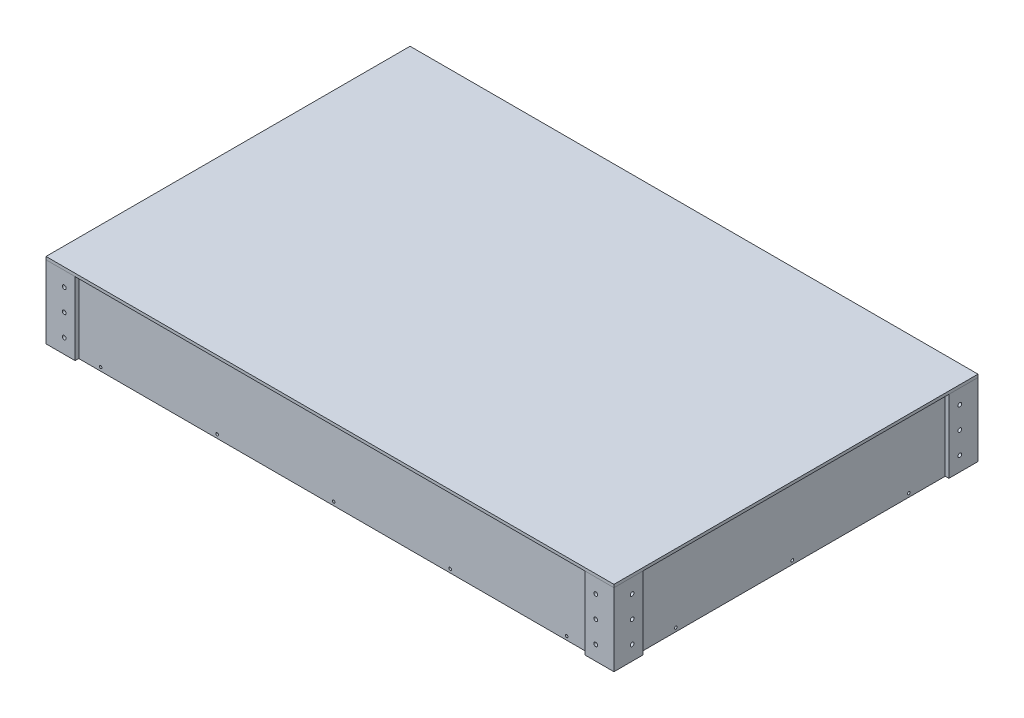
SolidWorks part; units mm, degrees
ref_plane "Front" through (0, 0, 0) normal (0, 0, 1) x (1, 0, 0)
ref_plane "Top" through (0, 0, 0) normal (0, 1, 0) x (1, 0, 0)
ref_plane "Right" through (0, 0, 0) normal (1, 0, 0) x (0, 0, -1)
sketch "Sketch1" plane through (0, 0, 0) normal (0, 1, 0) x (1, 0, 0)
  line L1 (-241.3, 152.4) -> (241.3, 152.4)
  line L2 (-241.3, 152.4) -> (-241.3, -152.4)
  line L3 (-241.3, -152.4) -> (241.3, -152.4)
  line L4 (241.3, 152.4) -> (241.3, -152.4)
  line L5 (-241.3, 152.4) -> (241.3, -152.4) construction
  line L6 (-241.3, -152.4) -> (241.3, 152.4) construction
  point P0 (0, 0)
  dimension "D1" = 482.6
  dimension "D2" = 304.8
extrude "Boss-Extrude1" add sketch "Sketch1" along normal blind 6.35
sketch "Sketch2" plane through (0, 6.35, 0) normal (0, 1, 0) x (1, 0, 0)
  line L0 (241.3, -152.4) -> (241.3, 152.4) construction
  line L1 (-241.3, 152.4) -> (241.3, 152.4)
  line L2 (-241.3, 152.4) -> (-241.3, 155.575)
  line L3 (-241.3, 155.575) -> (241.3, 155.575)
  line L4 (241.3, 152.4) -> (241.3, 155.575)
  line L5 (-241.3, 152.4) -> (241.3, 155.575) construction
  line L6 (-241.3, 155.575) -> (241.3, 152.4) construction
  line L7 (-241.3, -155.575) -> (241.3, -155.575)
  line L8 (-241.3, -155.575) -> (-241.3, -152.4)
  line L9 (-241.3, -152.4) -> (241.3, -152.4)
  line L10 (241.3, -155.575) -> (241.3, -152.4)
  line L11 (-241.3, -155.575) -> (241.3, -152.4) construction
  line L12 (-241.3, -152.4) -> (241.3, -155.575) construction
  line L13 (-241.3, 152.4) -> (-241.3, -152.4) construction
  line L14 (241.3, 152.4) -> (-241.3, 152.4) construction
  line L15 (-241.3, -152.4) -> (241.3, -152.4) construction
  point P0 (0, 153.9875)
  point P5 (0, -153.9875)
  dimension "D1" = 3.175
extrude "Boss-Extrude2" add sketch "Sketch2" along normal blind 57.15 and the other way up to surface (6.35 mm away) separate body other way up to face at (0, 0, 0)
sketch "Sketch3" plane through (0, 6.35, 0) normal (0, 1, 0) x (1, 0, 0)
  line L0 (241.3, -155.575) -> (-241.3, -155.575) construction
  line L1 (-241.3, 155.575) -> (-244.475, 155.575)
  line L2 (-241.3, 155.575) -> (-241.3, -155.575)
  line L3 (-241.3, -155.575) -> (-244.475, -155.575)
  line L4 (-244.475, 155.575) -> (-244.475, -155.575)
  line L6 (241.3, 155.575) -> (244.475, 155.575)
  line L7 (241.3, 155.575) -> (241.3, -155.575)
  line L8 (241.3, -155.575) -> (244.475, -155.575)
  line L9 (244.475, 155.575) -> (244.475, -155.575)
  dimension "D1" = 3.175
extrude "Boss-Extrude3" add sketch "Sketch3" along normal up to surface (57.15 mm away) and the other way up to surface (6.35 mm away) separate body up to face at (0, 63.5, -153.9875) other way up to face at (0, 0, 0)
sketch "Sketch4" plane through (0, 0, 0) normal (0, -1, 0) x (1, 0, 0)
  line L0 (-244.475, -155.575) -> (-222.25, -155.575)
  line L2 (-222.25, -155.575) -> (-222.25, -158.75)
  line L3 (-222.25, -158.75) -> (-247.65, -158.75)
  line L4 (-247.65, -158.75) -> (-247.65, -133.35)
  line L5 (-247.65, -133.35) -> (-244.475, -133.35)
  line L7 (-244.475, -133.35) -> (-244.475, -155.575)
  line L8 (-244.475, 155.575) -> (-244.475, -155.575) construction
  line L9 (-241.3, -155.575) -> (241.3, -155.575) construction
  dimension "D1" = 3.175
  dimension "D2" = 25.4
  dimension "D3" = 25.4
extrude "Boss-Extrude4" add sketch "Sketch4" against normal up to surface (63.5 mm away) separate body up to face at (0, 63.5, -153.9875)
mirror "Mirror1" about plane through (0, 0, 0) normal (1, 0, 0) of bodies 184
mirror "Mirror2" about plane through (0, 0, 0) normal (0, 0, 1) of bodies 184 185
sketch "Sketch5" plane through (0, 0, -155.575) normal (0, 0, -1) x (-1, 0, 0)
  line L0 (-241.3, 31.75) -> (-222.25, 31.75) construction
  line L1 (-241.3, 0) -> (-241.3, 63.5) construction
  line L2 (-222.25, 63.5) -> (-222.25, 0) construction
  line L3 (-231.775, 50.8) -> (-231.775, 12.7) construction
  circle A0 centre (-231.775, 50.8) radius 1.651
  circle A1 centre (-231.775, 31.75) radius 1.651
  circle A2 centre (-231.775, 12.7) radius 1.651
  point P8 (-231.775, 31.75)
  dimension "D2" = 3.302
  dimension "D1" = 38.1
extrude "Cut-Extrude1" cut sketch "Sketch5" against normal through all
mirror "Mirror3" about plane through (0, 0, 0) normal (1, 0, 0) of "Cut-Extrude1"
sketch "Sketch6" plane through (-247.65, 0, 0) normal (-1, 0, 0) x (0, 0, 1)
  line L0 (-152.4, 31.75) -> (-133.35, 31.75) construction
  line L1 (-133.35, 63.5) -> (-133.35, 0) construction
  line L2 (-152.4, 0) -> (-152.4, 63.5) construction
  line L3 (-142.875, 50.8) -> (-142.875, 12.7) construction
  circle A0 centre (-142.875, 50.8) radius 1.651
  circle A1 centre (-142.875, 31.75) radius 1.651
  circle A2 centre (-142.875, 12.7) radius 1.651
  point P2 (-142.875, 31.75)
  point P5 (-142.875, 31.75)
  dimension "D2" = 3.302
  dimension "D1" = 38.1
extrude "Cut-Extrude2" cut sketch "Sketch6" against normal through all
mirror "Mirror4" about plane through (0, 0, 0) normal (0, 0, 1) of "Cut-Extrude2"
sketch "Sketch7" plane through (0, 0, 155.575) normal (0, 0, 1) x (1, 0, 0)
  line L0 (-247.65, 3.175) -> (247.65, 3.175) construction
  line L1 (-247.65, 6.35) -> (-247.65, 0) construction
  line L2 (241.3, 0) -> (-241.3, 0) construction
  line L3 (-241.3, 6.35) -> (241.3, 6.35) construction
  line L4 (247.65, 63.5) -> (247.65, 0) construction
  circle A0 centre (-203.2, 3.175) radius 1.1811
  circle A1 centre (0, 3.175) radius 1.1811
  circle A2 centre (203.2, 3.175) radius 1.1811
  circle A3 centre (101.6, 3.175) radius 1.1811
  circle A4 centre (-101.6, 3.175) radius 1.1811
  dimension "D1" = 2.3622
  dimension "D3" = 2.3622
  dimension "D4" = 101.6
  dimension "D5" = 101.6
  dimension "D6" = 203.2
  dimension "D2" = 203.2
extrude "Cut-Extrude3" cut sketch "Sketch7" against normal through all and the other way through all
sketch "Sketch8" plane through (244.475, 0, 0) normal (1, 0, 0) x (0, 0, -1)
  line L0 (-158.75, 3.175) -> (158.75, 3.175) construction
  line L1 (-158.75, 63.5) -> (-158.75, 0) construction
  line L2 (158.75, 63.5) -> (158.75, 0) construction
  line L3 (0, 0) -> (0, 6.35) construction
  line L4 (-152.4, 6.35) -> (152.4, 6.35) construction
  circle A0 centre (0, 3.175) radius 1.1811
  circle A1 centre (101.6, 3.175) radius 1.1811
  circle A2 centre (-101.6, 3.175) radius 1.1811
  point P12 (0, 3.175)
  dimension "D1" = 2.3622
  dimension "D2" = 101.6
  dimension "D3" = 101.6
extrude "Cut-Extrude4" cut sketch "Sketch8" against normal through all
sketch "Sketch9" plane through (0, 63.5, 0) normal (0, 1, 0) x (1, 0, 0)
  line L1 (247.65, -158.75) -> (-247.65, -158.75)
  line L2 (247.65, -158.75) -> (247.65, 158.75)
  line L3 (247.65, 158.75) -> (-247.65, 158.75)
  line L4 (-247.65, -158.75) -> (-247.65, 158.75)
extrude "Boss-Extrude5" add sketch "Sketch9" along normal blind 2.54 separate body
sketch "Sketch10" [suppressed] plane through (0, 66.04, 0) normal (0, 1, 0) x (1, 0, 0)
  line L0 (0, 0) -> (0, -133.35) construction
  line L1 (0, -133.35) -> (52.3875, -133.35) construction
  line L2 (0, -133.35) -> (-52.3875, -133.35) construction
  line L3 (-247.65, -158.75) -> (247.65, -158.75) construction
  circle A0 centre (52.3875, -133.35) radius 3.175
  circle A1 centre (-52.3875, -133.35) radius 3.175
  dimension "D2" = 6.35
  dimension "D1" = 104.775
  dimension "D3" = 25.4
extrude "Cut-Extrude5" [suppressed] cut sketch "Sketch10" against normal through all
sketch "Sketch11" plane through (0, 0, -155.575) normal (0, 0, -1) x (-1, 0, 0)
  line L0 (0, 0) -> (0, 57.15) construction
  line L1 (0, 57.15) -> (-215.9, 57.15) construction
  line L2 (0, 57.15) -> (215.9, 57.15) construction
  circle A0 centre (-215.9, 57.15) radius 1.651
  circle A1 centre (-107.95, 57.15) radius 1.651
  circle A2 centre (0, 57.15) radius 1.651
  circle A3 centre (107.95, 57.15) radius 1.651
  circle A4 centre (215.9, 57.15) radius 1.651
  dimension "D2" = 3.302
  dimension "D1" = 431.8
  dimension "D3" = 57.15
extrude "Cut-Extrude6" cut sketch "Sketch11" against normal up to next (3.175 mm away)
sketch "Sketch12" [suppressed] plane through (0, 66.04, 0) normal (0, 1, 0) x (1, 0, 0)
  line L0 (0, 0) -> (0, 158.75) construction
  line L1 (247.65, 158.75) -> (-247.65, 158.75) construction
  line L2 (0, 146.05) -> (-215.9, 146.05) construction
  line L3 (0, 146.05) -> (215.9, 146.05) construction
  circle A0 centre (-215.9, 146.05) radius 1.651
  circle A1 centre (0, 146.05) radius 1.651
  circle A2 centre (215.9, 146.05) radius 1.651
  circle A3 centre (107.95, 146.05) radius 1.651
  circle A4 centre (-107.95, 146.05) radius 1.651
  dimension "D2" = 3.302
  dimension "D1" = 431.8
  dimension "D3" = 12.7
extrude "Cut-Extrude7" [suppressed] cut sketch "Sketch12" against normal through all
sketch "Sketch13" plane through (0, 6.35, 0) normal (0, 1, 0) x (1, 0, 0)
  line L1 (-228.6, 127) -> (228.6, 127) construction
  line L2 (-228.6, 127) -> (-228.6, -127) construction
  line L3 (-228.6, -127) -> (228.6, -127) construction
  line L4 (228.6, 127) -> (228.6, -127) construction
  line L5 (-228.6, 127) -> (228.6, -127) construction
  line L6 (-228.6, -127) -> (228.6, 127) construction
  circle A0 centre (-228.6, 127) radius 1.651
  circle A1 centre (228.6, 127) radius 1.651
  circle A2 centre (228.6, -127) radius 1.651
  circle A3 centre (-228.6, -127) radius 1.651
  point P0 (0, 0)
  dimension "D3" = 3.302
  dimension "D1" = 457.2
  dimension "D2" = 254
extrude "Cut-Extrude8" cut sketch "Sketch13" against normal through all
sketch "Sketch14" plane through (0, 6.35, 0) normal (0, 1, 0) x (1, 0, 0)
  circle A0 centre (152.4, 127) radius 3.175 construction
  circle A1 centre (152.4, 127) radius 3.175 construction
  circle A2 centre (152.4, -127) radius 3.175 construction
  circle A3 centre (152.4, -127) radius 3.175 construction
  circle A4 centre (19.05, -127) radius 3.175 construction
  circle A5 centre (19.05, -127) radius 3.175 construction
  circle A6 centre (19.05, 127) radius 3.175 construction
  circle A7 centre (19.05, 127) radius 3.175 construction
  circle A8 centre (-114.3, 127) radius 3.175 construction
  circle A9 centre (-114.3, 127) radius 3.175 construction
  circle A10 centre (-114.3, -127) radius 3.175 construction
  circle A11 centre (-114.3, -127) radius 3.175 construction
  circle A12 centre (152.4, 127) radius 6.35
  circle A13 centre (152.4, -127) radius 6.35
  circle A14 centre (19.05, -127) radius 6.35
  circle A15 centre (19.05, 127) radius 6.35
  circle A16 centre (-114.3, 127) radius 6.35
  circle A17 centre (-114.3, -127) radius 6.35
  dimension "D1" = 12.7
extrude "Cut-Extrude9" cut sketch "Sketch14" against normal through all
